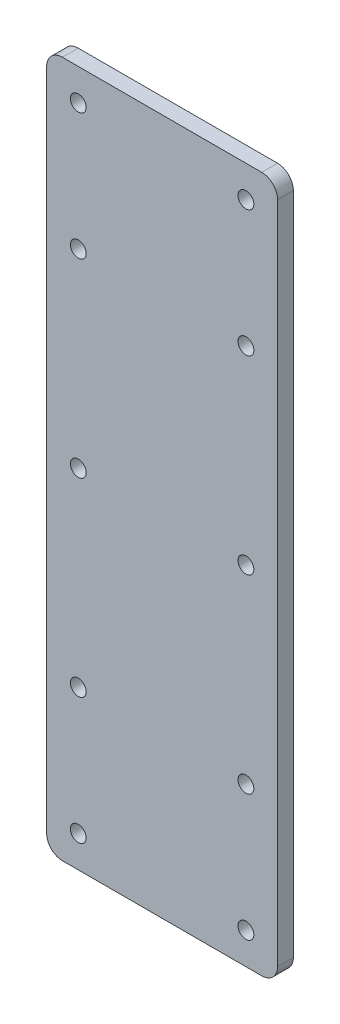
SolidWorks part; units mm, degrees
material "6061 Alloy"
ref_plane "Front Plane" through (0, 0, 0) normal (0, 0, 1) x (1, 0, 0)
ref_plane "Top Plane" through (0, 0, 0) normal (0, 1, 0) x (1, 0, 0)
ref_plane "Right Plane" through (0, 0, 0) normal (1, 0, 0) x (0, 0, -1)
sketch "Sketch2" plane through (0, 0, 0) normal (0, 0, 1) x (1, 0, 0)
  line L0 (36.5, 220) -> (36.5, 0) construction
  line L1 (5, 0) -> (68, 0)
  line L2 (0, 5) -> (0, 215)
  line L3 (5, 220) -> (68, 220)
  line L4 (73, 5) -> (73, 215)
  line L5 (10, 210) -> (63, 210)
  line L6 (10, 210) -> (10, 170)
  line L7 (10, 170) -> (63, 170)
  line L8 (63, 210) -> (63, 170)
  line L9 (0, 110) -> (73, 110) construction
  line L10 (10, 50) -> (63, 50)
  line L11 (10, 50) -> (10, 10)
  line L12 (10, 10) -> (63, 10)
  line L13 (63, 50) -> (63, 10)
  circle A0 centre (10, 210) radius 2.5
  circle A1 centre (63, 210) radius 2.5
  circle A2 centre (63, 170) radius 2.5
  circle A3 centre (10, 170) radius 2.5
  circle A4 centre (63, 50) radius 2.5
  circle A5 centre (10, 50) radius 2.5
  circle A6 centre (10, 10) radius 2.5
  circle A7 centre (63, 10) radius 2.5
  circle A8 centre (10, 110) radius 2.5
  circle A9 centre (63, 110) radius 2.5
  arc A10 (5, 0) -> (0, 5) centre (5, 5) cw
  arc A11 (68, 0) -> (73, 5) centre (68, 5) ccw
  arc A12 (68, 220) -> (73, 215) centre (68, 215) cw
  arc A13 (0, 215) -> (5, 220) centre (5, 215) cw
  point P11 (36.5, 210)
  point P20 (36.5, 10)
  point P31 (0, 0)
  point P34 (0, 0)
  dimension "D5" = 5
  dimension "D8" = 5
  dimension "D1" = 53
  dimension "D2" = 40
  dimension "D3" = 10
  dimension "D4" = 10
  dimension "D6" = 120
  dimension "D7" = 10
extrude "Boss-Extrude1" add sketch "Sketch2" along normal blind 5 contours A13 L2 A10 L1 A11 L4 A12 L3 A9 A8 A7 L12 A6 L11 A5 L10 A4 L13 A3 L6 A0 L5 A1 L8 A2 L7 | A3 L7 A2 L8 A1 L5 A0 L6 | A7 L13 A4 L10 A5 L11 A6 L12 region at (36.5, 110, 0) region at (36.5, 190, 0) region at (36.5, 30, 0)
